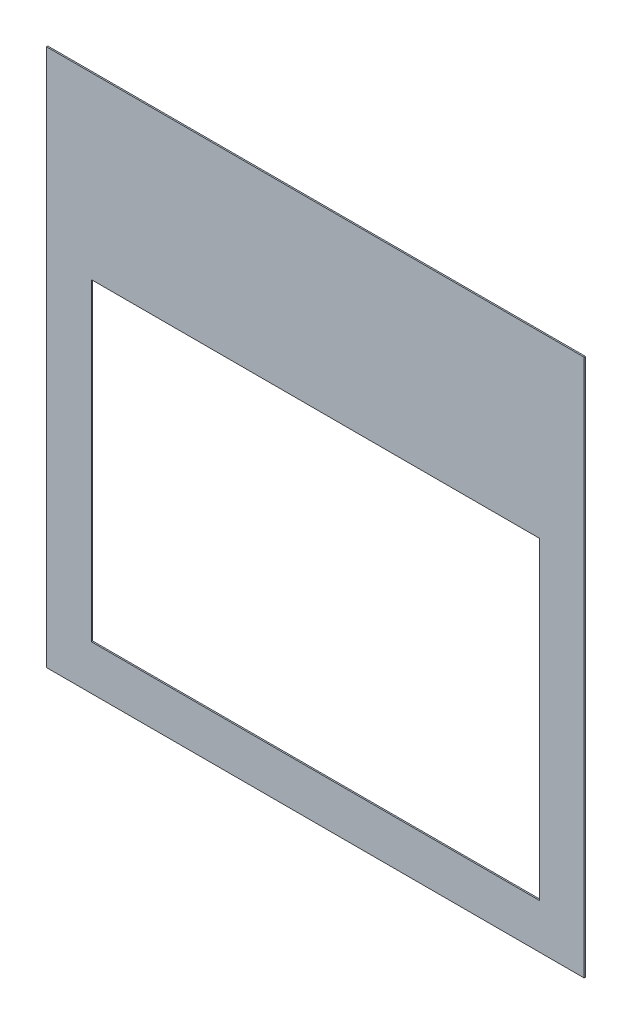
SolidWorks part; units mm, degrees
material "AISI 304"
ref_plane "Front Plane" through (0, 0, 0) normal (0, 0, 1) x (1, 0, 0)
ref_plane "Top Plane" through (0, 0, 0) normal (0, 1, 0) x (1, 0, 0)
ref_plane "Right Plane" through (0, 0, 0) normal (1, 0, 0) x (0, 0, -1)
sketch "Sketch1" plane through (0, 0, 0) normal (0, 0, 1) x (1, 0, 0)
  line L0 (-500, -400) -> (500, -400)
  line L1 (-600, 0) -> (600, 0)
  line L2 (-600, 0) -> (-600, -1200)
  line L3 (-600, -1200) -> (600, -1200)
  line L4 (600, 0) -> (600, -1200)
  line L5 (500, -400) -> (500, -1100)
  line L6 (-500, -1100) -> (500, -1100)
  line L7 (-500, -400) -> (-500, -1100)
  point P4 (0, 0)
  point P10 (0, -400)
  dimension "D1" = 1200
  dimension "D2" = 1200
  dimension "D3" = 400
  dimension "D4" = 100
  dimension "D5" = 100
base flange "Base-Flange1" sketch "Sketch1" thickness 3 reverse thickness direction no parameters "D1"=0.7366
sketch "Bend-Lines1" [suppressed] plane through (0, 0, 0) normal (0, 1, 0) x (1, 0, 0)
sketch "Bounding-Box1" [suppressed] plane through (0, 0, 0) normal (0, 1, 0) x (1, 0, 0)
sheet metal parameters "Sheet-Metal1" thickness 3 parameters "D1"=0.7366
flat pattern "Flat-Pattern1" [suppressed]
sketch "Bend-Lines2" plane through (0, 0, 0) normal (0, 1, 0) x (1, 0, 0)
sketch3d "Bounding-Box2" [suppressed]
  line L0 (-600, -1200, 0) -> (600, -1200, 0) construction
  line L1 (-600, 0, 0) -> (600, 0, 0) construction
  line L2 (-600, -1200, 0) -> (-600, 0, 0) construction
  line L3 (600, -1200, 0) -> (600, 0, 0) construction
